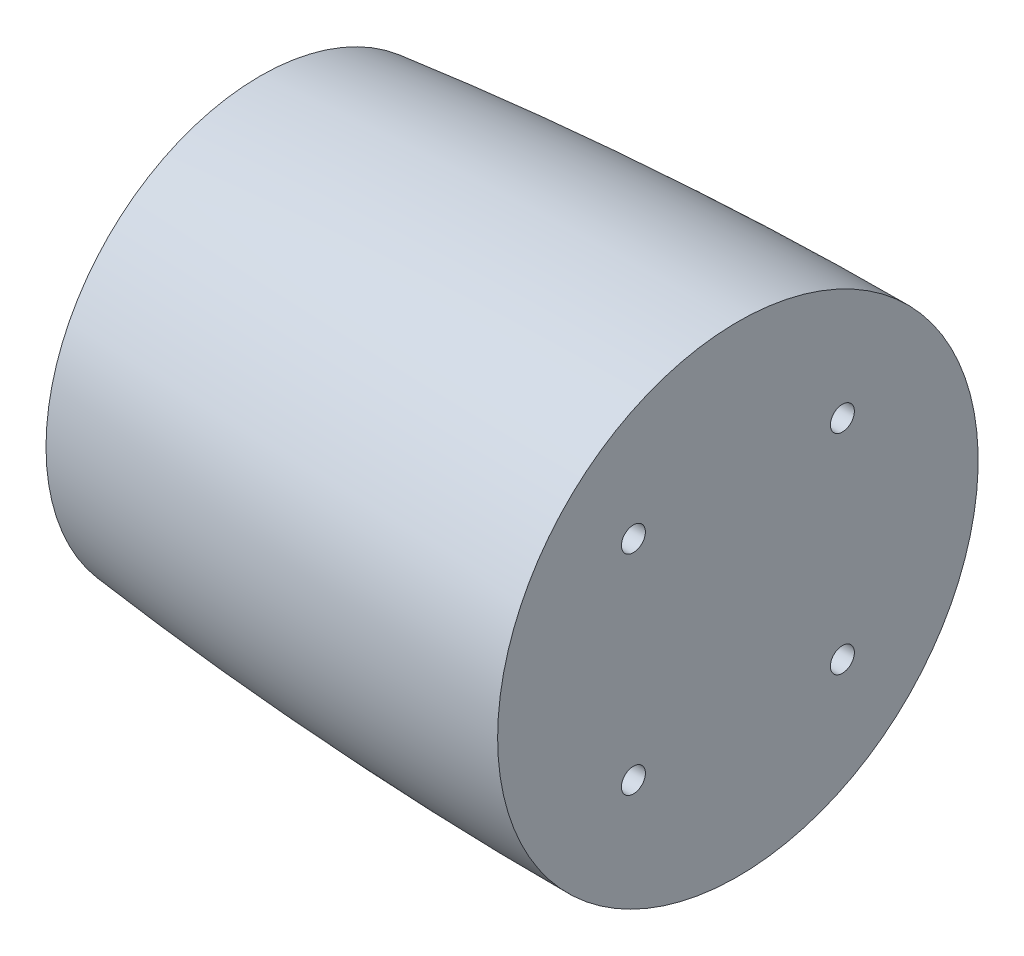
SolidWorks part; units mm, degrees
ref_plane "Front Plane" through (0, 0, 0) normal (0, 0, 1) x (1, 0, 0)
ref_plane "Top Plane" through (0, 0, 0) normal (0, 1, 0) x (1, 0, 0)
ref_plane "Right Plane" through (0, 0, 0) normal (1, 0, 0) x (0, 0, -1)
sketch "Sketch1" plane through (0, 0, 0) normal (0, 0, 1) x (1, 0, 0)
  line L0 (0, 0) -> (101.6, 0)
  line L1 (0, 0) -> (0, 45.5653)
  line L2 (101.6, 0) -> (101.6, 51.1048)
  spline S0 degree 9 poles (-10.1117, 44.4037) (3.4296, 46.0341) (16.9709, 47.439) (30.5122, 48.6198) (44.0535, 49.5779) (57.5948, 50.314) (71.1361, 50.829) (84.6774, 51.1232) (98.2187, 51.1968) (111.76, 51.0496) knots 0 0 0 0 0 0 0 0 0 0 1 1 1 1 1 1 1 1 1 1 construction
  spline S1 degree 9 poles (0, 45.5653) (11.2889, 46.8) (22.5778, 47.8785) (33.8667, 48.8016) (45.1556, 49.57) (56.4444, 50.1842) (67.7333, 50.6445) (79.0222, 50.9514) (90.3111, 51.1048) (101.6, 51.1048) knots 0.08297 0.08297 0.08297 0.08297 0.08297 0.08297 0.08297 0.08297 0.08297 0.08297 0.916634 0.916634 0.916634 0.916634 0.916634 0.916634 0.916634 0.916634 0.916634 0.916634
  dimension "D1" = 101.6
  dimension "D2" = 51.1048
  dimension "D3" = 45.5653
revolve "Revolve1" add sketch "Sketch1" angle 360 about L0
hole_wizard "1/4-20 Tapped Hole1" positions "Sketch5" profile "Sketch6" tap size "1/4-20" standard "ANSI Inch" end condition through all
sketch "Sketch5" plane through (101.6, 0, 0) normal (1, 0, 0) x (0, 0, -1)
  line L6 (0, 0) -> (0, 29.7991) construction
  line L8 (0, 0) -> (-36.7734, 0) construction
  point P0 (-22.225, 22.225)
  point P33 (0, 0)
  point P34 (22.225, 22.225)
  point P35 (0, 0)
  point P36 (22.225, -22.225)
  point P37 (-22.225, -22.225)
  dimension "D1" = 44.45
  dimension "1.75" = 44.45
sketch "Sketch6" plane through (101.6, 22.225, 22.225) normal (0, 1, 0) x (0, 0, -1)
  line L0 (0, 0) -> (0, 101.6)
  line L1 (0, 101.6) -> (2.5527, 101.6)
  line L2 (2.5527, 101.6) -> (2.5527, 0)
  line L5 (2.5527, 0) -> (0, 0)
  line L11 (0, -6.35) -> (0, 107.95) construction
  dimension "Thru Tap Drill Dia." = 5.1054
  dimension "Thru Tap Drill Depth" = 101.6
